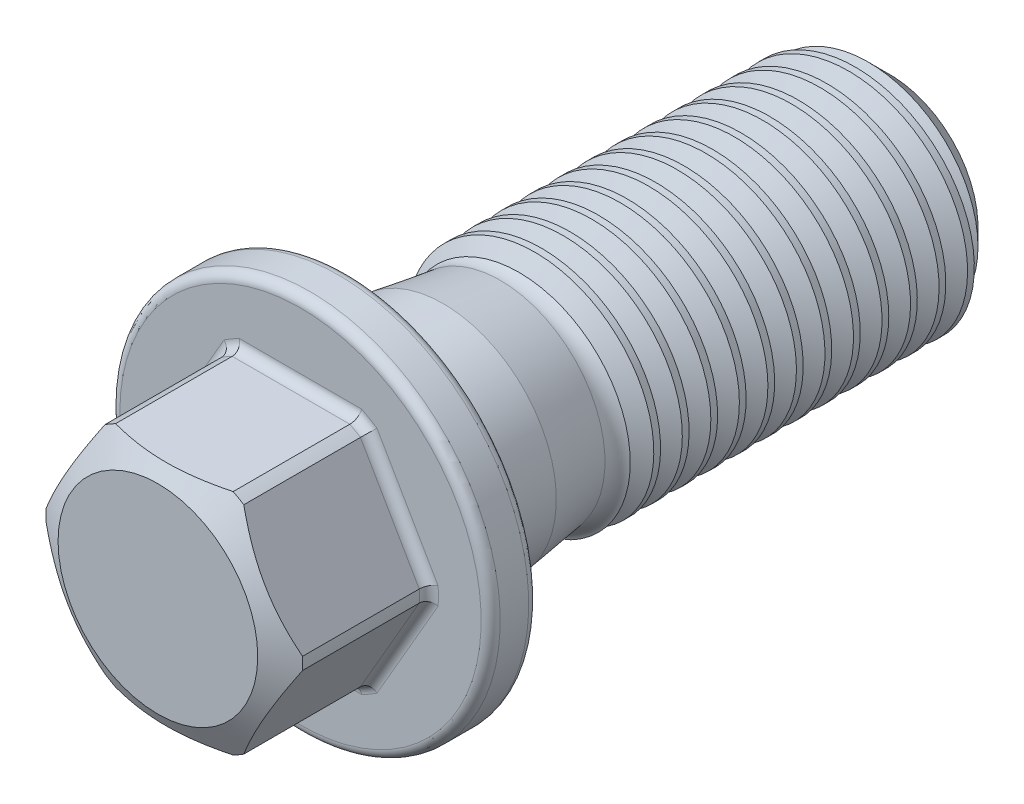
SolidWorks part; units mm, degrees
ref_plane "Front Plane" through (0, 0, 0) normal (0, 0, 1) x (1, 0, 0)
ref_plane "Top Plane" through (0, 0, 0) normal (0, 1, 0) x (1, 0, 0)
ref_plane "Right Plane" through (0, 0, 0) normal (1, 0, 0) x (0, 0, -1)
sketch "Sketch1" plane through (0, 0, 0) normal (1, 0, 0) x (0, 0, -1)
  line L0 (0, 0) -> (-77, 0)
  line L1 (-62, 13.5) -> (-75.2679, 13.5)
  line L2 (-77, 0) -> (-77, 10.5)
  line L3 (-62, 13.5) -> (-62, 19)
  line L4 (-58, 20) -> (-61, 20)
  line L5 (-62, 0) -> (-62, 30.5619) construction
  line L6 (0, 13.5) -> (-77, 13.5) construction
  line L7 (-57, 12.9) -> (-57, 19)
  line L8 (0, 20) -> (-77, 20) construction
  line L9 (-77, 0) -> (-77, 30.5619) construction
  line L11 (-57, 13.5) -> (-57, 20) construction
  line L12 (-62, 13.5) -> (-62, 20) construction
  line L14 (-3, 12.25) -> (-38.8561, 12.25)
  line L15 (-47, 11.9) -> (-41, 11.0211)
  line L16 (0, 9.25) -> (0, 0)
  line L19 (-47, 11.9) -> (-56, 11.9)
  line L22 (0, 9.25) -> (-3, 12.25)
  line L23 (-75.2679, 13.5) -> (-77, 10.5)
  line L24 (0, 12.25) -> (-77, 12.25) construction
  arc A0 (-57, 19) -> (-58, 20) centre (-58, 19) ccw
  arc A2 (-62, 14.5) -> (-63, 13.5) centre (-63, 14.5) cw construction
  arc A3 (-56, 11.9) -> (-57, 12.9) centre (-56, 12.9) cw
  arc A4 (-61, 20) -> (-62, 19) centre (-61, 19) ccw
  arc A5 (-38.8561, 12.25) -> (-41, 11.0211) centre (-40.7101, 13) cw
  point P14 (0, 11)
  point P15 (-77, 11)
  point P17 (0, 12.25)
  point P18 (-77, 11.9)
  point P23 (-36, 0)
  point P24 (-47, 12.25)
  point P25 (-47, 0)
  dimension "D2" = 11
  dimension "D3" = 1
  dimension "D12" = 47
  dimension "D13" = 8.333
  dimension "D16" = 1
  dimension "D19" = 2
  dimension "D1" = 77
  dimension "D4" = 13.5
  dimension "D5" = 11.9
  dimension "D6" = 12.25
  dimension "D7" = 41
  dimension "D8" = 20
  dimension "D9" = 15
  dimension "D10" = 5
  dimension "D11" = 57
  dimension "D14" = 3
  dimension "D15" = 45
  dimension "D17" = 30
  dimension "D18" = 10.5
revolve "Revolve1" add sketch "Sketch1" angle 360 about L0
sketch "Sketch2" plane through (0, 0, 77) normal (0, 0, 1) x (1, 0, 0)
  line L0 (-8.3716, 14.5) -> (-16.7432, 0)
  line L1 (13.8564, 0) -> (6.9282, 12)
  line L2 (6.9282, 12) -> (-6.9282, 12)
  line L3 (-6.9282, 12) -> (-13.8564, 0)
  line L4 (-13.8564, 0) -> (-6.9282, -12)
  line L5 (-6.9282, -12) -> (6.9282, -12)
  line L6 (6.9282, -12) -> (13.8564, 0)
  line L7 (-16.7432, 0) -> (-8.3716, -14.5)
  line L8 (-8.3716, -14.5) -> (8.3716, -14.5)
  line L9 (8.3716, -14.5) -> (16.7432, 0)
  line L10 (16.7432, 0) -> (8.3716, 14.5)
  line L11 (8.3716, 14.5) -> (-8.3716, 14.5)
  circle A0 centre (0, 0) radius 12 construction
  dimension "D1" = 24
  dimension "D2" = 24
  dimension "D3" = 2.5
extrude "Cut-Extrude1" cut sketch "Sketch2" against normal up to surface (15 mm away) up to face at (-13.5, 0, 62)
sketch "Sketch3" plane through (0, 0, 0) normal (0, 0, -1) x (-1, 0, 0)
  circle A0 centre (0, 0) radius 12.25 construction
  circle A1 centre (0, 0) radius 12.25
sketch "Sketch4" plane through (0, 0, 0) normal (1, 0, 0) x (0, 0, -1)
  line L0 (0, -9.25) -> (0, 9.25) construction
  line L1 (0, 10.2685) -> (1.4995, 12.8657)
  line L2 (1.4995, 12.8657) -> (-1.4995, 12.8657)
  line L3 (-1.4995, 12.8657) -> (0, 10.2685)
  circle A0 centre (0, 12) radius 0.8657 construction
  dimension "D1" = 2.999
  dimension "D2" = 12
sketch "Sketch8" plane through (-0.3627, -1.0356, 77) normal (0, 0, 1) x (1, 0, 0)
  line L26 (0, 0) -> (-6.0227, 3.7297) construction
  line L27 (0, 0) -> (7.174, 0.4051) construction
  arc A0 (7.174, 0.4051) -> (-6.3795, 3.3064) centre (0, 0) ccw construction
  text T0 "JOB NO#" font "Calibri" height 2
  dimension "D1" = 145
sketch "Sketch10" plane through (-0.3627, -1.0356, 77) normal (0, 0, 1) x (1, 0, 0)
  line L2 (0, 0) -> (7.174, 0.4051) construction
  line L3 (0, 0) -> (-6.0227, 3.7297) construction
  arc A1 (7.174, 0.4051) -> (-6.3795, 3.3064) centre (0, 0) ccw construction
  text T0 "JOB NO#" font "Calibri" height 2
sketch "Sketch13" plane through (0, 0, 0) normal (0, 0, -1) x (-1, 0, 0)
  circle A0 centre (0, 0) radius 11.9118
curve "Helix/Spiral2" pitch 3 height 40.5 radius 11.9118 centre (0, 0, 0) axis (0, 0, 1) start towards (0, 1, 0)
sweep "Cut-Sweep3" cut profiles "Sketch4" path "Helix/Spiral2" align with end faces yes
fillet "Fillet1" radius 1 12 edges at (13.5, 0, 62) (10.3923, -6, 62) (6.75, -11.6913, 62) (0, -12, 62) (-6.75, -11.6913, 62) (-10.3923, -6, 62) (-13.5, 0, 62) (-10.3923, 6, 62) (-6.75, 11.6913, 62) (6.75, 11.6913, 62) (0, 12, 62) (10.3923, 6, 62)
